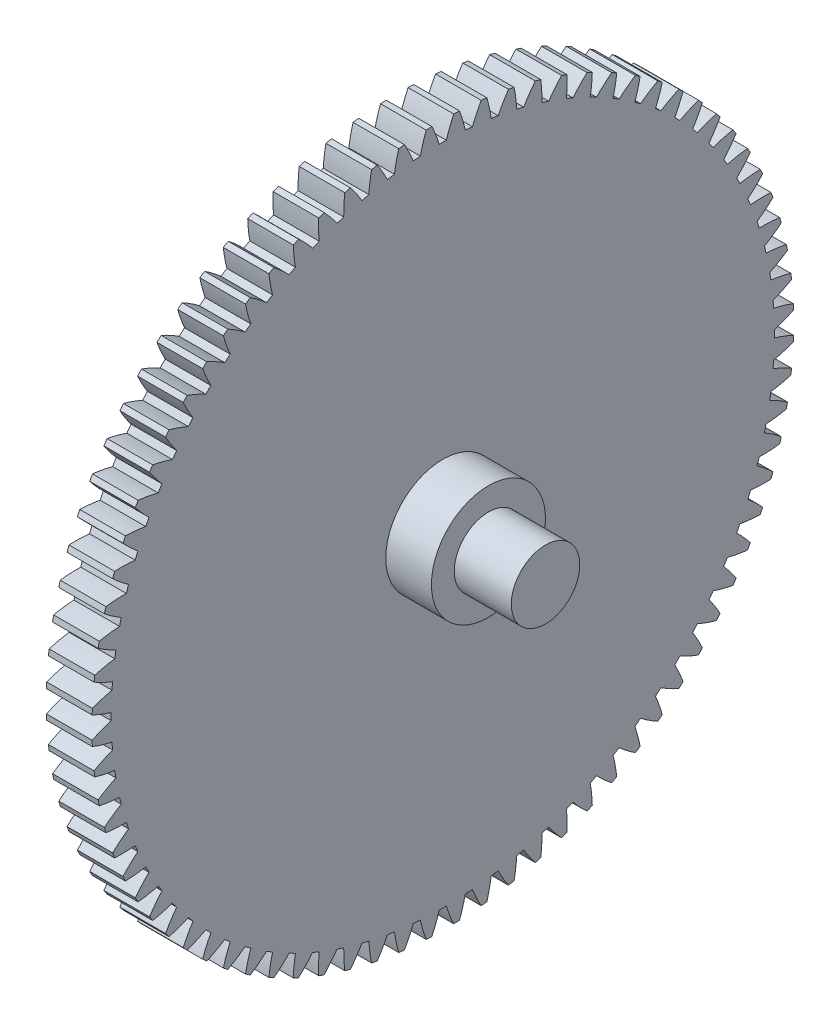
SolidWorks part; units mm, degrees
ref_plane "Plane1" through (0, 0, 0) normal (0, 0, 1) x (1, 0, 0)
ref_plane "Plane2" through (0, 0, 0) normal (0, 1, 0) x (1, 0, 0)
ref_plane "Plane3" through (0, 0, 0) normal (1, 0, 0) x (0, 0, -1)
sketch "HoldingSke" plane through (0, 0, 0) normal (0, 1, 0) x (1, 0, 0)
  line L0 (0, 0) -> (0.1158, -0.6565)
  line L1 (-15, 0) -> (100, 0) construction
  line L2 (0, 0) -> (-2.1039, 2.3779)
  line L3 (0, 0) -> (-11.863, 4.5341)
  line L4 (0, 0) -> (1.4996, 8.5048)
  line L5 (0, 0) -> (-46.8476, -17.4728)
  line L6 (0, 0) -> (-6.6317, -4.4744)
  line L7 (-2.1039, 2.3779) -> (8.6586, 51.2059)
  line L8 (-76.2, 54.61) -> (-74.4, 54.61)
  line L9 (-71.009, 38.7566) -> (-53.1078, 45.2721)
  line L10 (-76.2, 71.12) -> (104.1128, 71.12)
  line L11 (0, 0) -> (-8, 0)
  line L12 (-76.2, 101.6) -> (-76.147, 101.6)
  line L13 (24.9733, 27.94) -> (52.9518, 28.4284)
  line L14 (24.9733, 27.94) -> (24.9743, 27.94)
  line L15 (24.9733, 27.94) -> (100.4006, 29.5858)
  line L16 (-63.627, -1.5) -> (-12.827, -1.5)
  circle A0 centre (0, 0) radius 5
  circle A1 centre (0, 0) radius 37.5
  circle A2 centre (0, 0) radius 37.5
  circle A3 centre (0, 0) radius 5
  dimension "Num_teeth" = 80
  dimension "Pitch_radius" = 180.3128
  dimension "Width" = 8
  dimension "Thickness" = 8
sketch "BasProSke" plane through (0, 0, 0) normal (0, 1, 0) x (1, 0, 0)
  line L0 (-10, 0) -> (60, 0) construction
  line L1 (0, 0) -> (0, 61.5)
  line L2 (0, 0) -> (8, 0)
  line L3 (8, 0) -> (8, 61.5)
  line L4 (8, 61.5) -> (0, 61.5)
  dimension "Thickness" = 8
  dimension "Diameter" = 123
revolve "Base-Revolve" add sketch "BasProSke" angle 360 about L0
sketch "TooCutSke" plane through (0, 0, 0) normal (1, 0, 0) x (0, 0, -1)
  line L1 (0, 0) -> (0, 107) construction
  line L2 (0, 0) -> (-1.2708, 59.9865) construction
  line L3 (0, 0) -> (-4.7104, 119.8879) construction
  line L4 (-1.2708, 59.9865) -> (-2.3552, 59.9439) construction
  arc A0 (0.6242, 58.1206) -> (-0.6242, 58.1206) centre (0, 0) ccw
  arc A1 (1.9247, 61.4953) -> (-1.9247, 61.4953) centre (0, 0) ccw
  circle A2 centre (0, 0) radius 60 construction
  circle A3 centre (0, 0) radius 56.3816 construction
  arc A4 (-0.6242, 58.1206) -> (-1.9247, 61.4953) centre (-23.6054, 51.2022) ccw
  arc A5 (1.9247, 61.4953) -> (0.6242, 58.1206) centre (23.6054, 51.2022) ccw
extrude "ToothCut" cut sketch "TooCutSke" along normal through all
fillet "Breaks" [suppressed] radius 0.03 tangent propagation no
fillet "RootFillets" [suppressed] radius 0.376
pattern_circular "TeethCuts" count 80 every 4.5 about axis through (-10, 0, 0) along (1, 0, 0) of "ToothCut", "RootFillets", "Breaks"
sketch "HubNeaOneSke" plane through (0, 0, 0) normal (-1, 0, 0) x (0, 0, 1)
  circle A0 centre (0, 0) radius 37.5
  dimension "Diameter" = 75
extrude "HubNearOne" [suppressed] add sketch "HubNeaOneSke" along normal blind 42.0001
sketch "HubNeaBotSke" plane through (0, 0, 0) normal (-1, 0, 0) x (0, 0, 1)
  circle A0 centre (0, 0) radius 37.5
  dimension "Diameter" = 75
extrude "HubNearBoth" [suppressed] add sketch "HubNeaBotSke" along normal blind 21
ref_plane "FarPln" through (8, 0, 0) normal (1, 0, 0) x (0, 0, -1)
sketch "HubFarSke" plane through (8, 0, 0) normal (1, 0, 0) x (0, 0, -1)
  circle A0 centre (0, 0) radius 37.5
  dimension "Diameter" = 75
extrude "HubFar" [suppressed] add sketch "HubFarSke" along normal blind 21
sketch "BorSke" plane through (0, 0, 0) normal (1, 0, 0) x (0, 0, -1)
  circle A0 centre (0, 0) radius 5
  dimension "Diameter" = 10
extrude "Bore" cut sketch "BorSke" along normal mid plane 100.0001
sketch "KeySke" plane through (0, 0, 0) normal (1, 0, 0) x (0, 0, -1)
  line L0 (-2, 0) -> (-2, 6.8)
  line L1 (-2, 6.8) -> (2, 6.8)
  line L2 (2, 6.8) -> (2, 0)
  line L3 (0, 0) -> (0, 34) construction
  line L4 (-2, 0) -> (2, 0)
  dimension "Width" = 4
extrude "Keyway" [suppressed] cut sketch "KeySke" along normal mid plane 100.0001
pattern_circular "Keyway2" [suppressed] count 2 every 90 about axis through (-10, 0, 0) along (1, 0, 0) reverse direction yes
sketch "Esboço1" plane through (8, 0, 0) normal (1, 0, 0) x (0, 0, -1)
  circle A0 centre (0, 0) radius 10
extrude "Ressalto-extrusão1" add sketch "Esboço1" along normal blind 8
sketch "Esboço2" plane through (16, 0, 0) normal (1, 0, 0) x (0, 0, -1)
  circle A0 centre (0, 0) radius 6
extrude "Ressalto-extrusão2" add sketch "Esboço2" along normal blind 10
equation "' \"Module@HoldingSke\" = 6.35"
equation "' \"Num_teeth@HoldingSke\" = 12"
equation "' \"Ap@HoldingSke\" =  20"
equation "' \"Ap@HoldingSke\" = 20"
equation "' \"Width@HoldingSke\" = 0.5 * 25.4"
equation "' \"Hub_dia@HoldingSke\"= 1 * 25.4"
equation "' \"Hub_dia@HoldingSke\" = 1 * 25.4"
equation "' \"Overall_len@HoldingSke\" = 1.0 * 25.4"
equation "' \"Bore@HoldingSke\" = 0.75 * 25.4"
equation "' \"T_dim@HoldingSke\" = 0.1 * 25.4"
equation "' \"Width@KeySke\" = 0.25 * 25.4"
equation "' \"Show_teeth@HoldingSke\" = 13"
equation "' \"Backlash@HoldingSke\" = 0.009 * 25.4"
equation "' \"Addendum_fac@HoldingSke\" = 1.0"
equation "' \"Dedendum_fac@HoldingSke\" = 1.25"
equation "' \"Dedendum_add@HoldingSke\" = 0.00005 * 25.4"
equation "' \"Clearance_fac@HoldingSke\" = 0.25"
equation "\"Pitch@HoldingSke\" = 1 / \"Module@HoldingSke\""
equation "\"Overcut_dia@TooCutSke\" = (\"Num_teeth@HoldingSke\" + 2 * \"Addendum_fac@HoldingSke\") / \"Pitch@HoldingSke\" + 0.002 * 25.4"
equation "\"Pitch_dia@TooCutSke\" = \"Num_teeth@HoldingSke\" / \"Pitch@HoldingSke\""
equation "\"Base_dia@TooCutSke\" = \"Num_teeth@HoldingSke\" / \"Pitch@HoldingSke\" * cos((\"Ap@HoldingSke\"  * 3.14159265 / 180))"
equation "\"Root_dia@TooCutSke\" = (\"Num_teeth@HoldingSke\" + 2) / \"Pitch@HoldingSke\" - 2 * (\"Addendum_fac@HoldingSke\" + \"Dedendum_fac@HoldingSke\") / \"Pitch@HoldingSke\" - \"Dedendum_add@HoldingSke\" * 2"
equation "\"Half_ang@TooCutSke\" = 180 / \"Num_teeth@HoldingSke\""
equation "\"Half_CT@TooCutSke\" = \"Num_teeth@HoldingSke\" / \"Pitch@HoldingSke\" * sin((3.14159265 / 2 / \"Num_teeth@HoldingSke\")) / 2 - 7 * \"Backlash@HoldingSke\" / 4"
equation "\"Flank_rad@TooCutSke\" = \"Num_teeth@HoldingSke\" / \"Pitch@HoldingSke\" / 5"
equation "\"Radius@RootFillets\" = \"Clearance_fac@HoldingSke\" / \"Pitch@HoldingSke\" + \"Dedendum_add@HoldingSke\""
equation "\"Break_rad@Breaks\" = 0.02 / \"Pitch@HoldingSke\""
equation "\"Thickness@HoldingSke\" = \"Width@HoldingSke\""
equation "\"OAL@HoldingSke\" = \"Thickness@HoldingSke\""
equation "\"MHD@HoldingSke\" = (\"Num_teeth@HoldingSke\" + 2) / \"Pitch@HoldingSke\" - 2 * (\"Addendum_fac@HoldingSke\" + \"Dedendum_fac@HoldingSke\")  / \"Pitch@HoldingSke\" - \"Dedendum_add@HoldingSke\" * 2"
equation "\"MBD@HoldingSke\" = (\"Num_teeth@HoldingSke\" + 2) / \"Pitch@HoldingSke\" - 2 * (\"Addendum_fac@HoldingSke\" + \"Dedendum_fac@HoldingSke\")  / \"Pitch@HoldingSke\" - \"Dedendum_add@HoldingSke\" * 2 - 0.002 * 25.4"
equation "\"MHD@HoldingSke\" = ((sgn( \"MHD@HoldingSke\" - \"Hub_dia@HoldingSke\" )-1)*( \"MHD@HoldingSke\" - \"Hub_dia@HoldingSke\" ))/-2+ \"Hub_dia@HoldingSke\""
equation "\"MBD@HoldingSke\" = ((sgn( \"MBD@HoldingSke\" - \"Bore@HoldingSke\" )-1)*( \"MBD@HoldingSke\" - \"Bore@HoldingSke\" ))/-2+ \"Bore@HoldingSke\""
equation "\"OAL@HoldingSke\" = ((sgn( \"OAL@HoldingSke\" - \"Overall_len@HoldingSke\" )+1)*( \"OAL@HoldingSke\" - \"Overall_len@HoldingSke\" ))/2 + \"Overall_len@HoldingSke\" + 0.000002 * 25.4"
equation "\"Num_teeth@TeethCuts\" = int( \"Show_teeth@HoldingSke\" ) + 1"
equation "\"Num_teeth@TeethCuts\" = ((sgn( \"Num_teeth@TeethCuts\" - \"Num_teeth@HoldingSke\" )-1)*( \"Num_teeth@TeethCuts\" - \"Num_teeth@HoldingSke\" ))/-2+ \"Num_teeth@HoldingSke\""
equation "\"Num_teeth@TeethCuts\" = ((sgn( \"Num_teeth@TeethCuts\" - 2.0)+1)*( \"Num_teeth@TeethCuts\" - 2.0))/2 +2.0"
equation "\"Angle@TeethCuts\" = 360.0 / \"Num_teeth@HoldingSke\""
equation "\"Diameter@BasProSke\" = (\"Num_teeth@HoldingSke\" + 2 * \"Addendum_fac@HoldingSke\") / \"Pitch@HoldingSke\""
equation "\"Thickness@BasProSke\"  = \"Thickness@HoldingSke\""
equation "' \"Fillet_rad@BasProSke\" =  \"Thickness@HoldingSke\" * 0.05"
equation "' \"Fillet_rad@BasProSke\" = \"Thickness@HoldingSke\" * 0.05"
equation "\"MHD@HoldingSke\" = ((sgn( \"MHD@HoldingSke\" - \"Root_dia@TooCutSke\" )-1)*( \"MHD@HoldingSke\" - \"Root_dia@TooCutSke\" ))/-2+ \"Root_dia@TooCutSke\""
equation "\"Diameter@HubNeaOneSke\" = \"MHD@HoldingSke\""
equation "\"Length@HubNearOne\" = \"OAL@HoldingSke\" - \"Thickness@BasProSke\""
equation "\"Diameter@HubNeaBotSke\" = \"MHD@HoldingSke\""
equation "\"Length@HubNearBoth\" = ( \"OAL@HoldingSke\" - \"Thickness@BasProSke\" ) / 2.0"
equation "\"Thickness@FarPln\" = \"Thickness@BasProSke\""
equation "\"Diameter@HubFarSke\" = \"MHD@HoldingSke\""
equation "\"Length@HubFar\" = ( \"OAL@HoldingSke\" - \"Thickness@BasProSke\" ) / 2.0"
equation "\"Diameter@BorSke\" = \"MBD@HoldingSke\""
equation "\"D1@Bore\" = \"OAL@HoldingSke\" * 2.0"
equation "\"D1@Keyway\" = \"OAL@HoldingSke\" * 2.0"
equation "\"Offset@KeySke\" = \"T_dim@HoldingSke\" + \"MBD@HoldingSke\" / 2.0"
